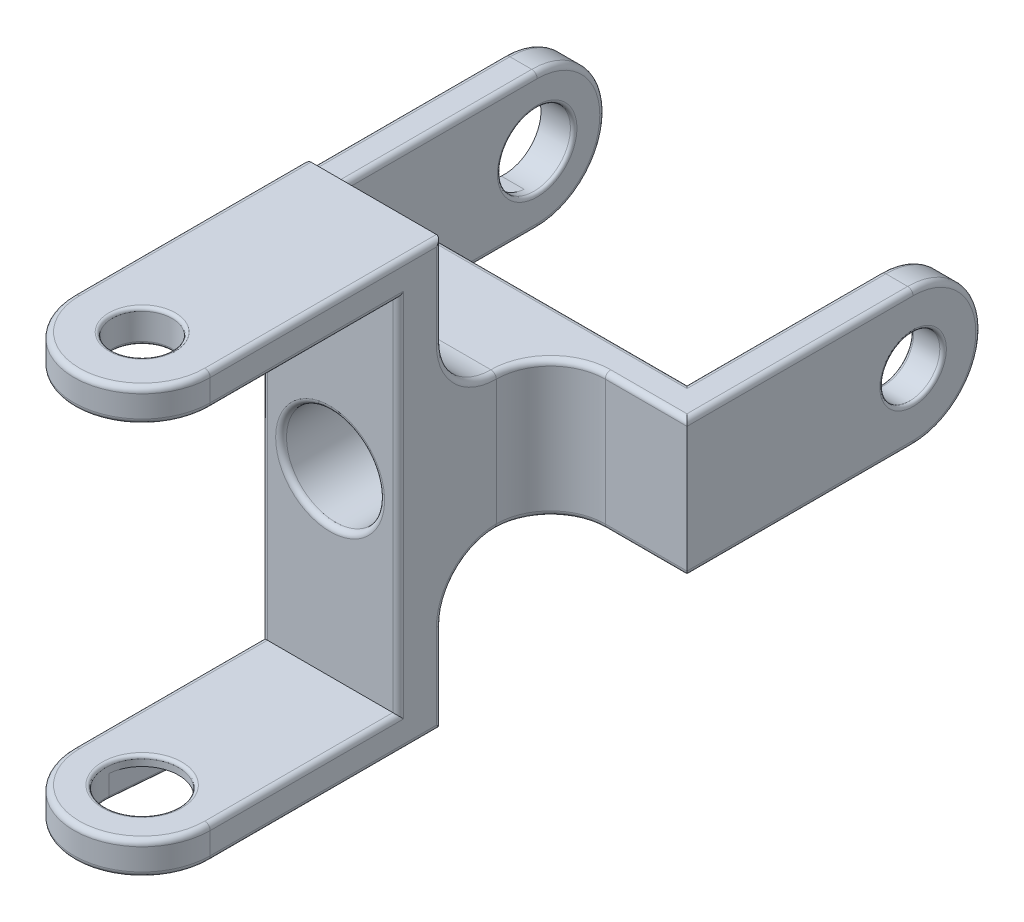
SolidWorks part; units mm, degrees
material "聚脂树脂"
ref_plane "前视基准面" through (0, 0, 0) normal (0, 0, 1) x (1, 0, 0)
ref_plane "上视基准面" through (0, 0, 0) normal (0, 1, 0) x (1, 0, 0)
ref_plane "右视基准面" through (0, 0, 0) normal (1, 0, 0) x (0, 0, -1)
sketch "草图1" plane through (0, 0, 0) normal (0, 0, 1) x (1, 0, 0)
  line L1 (-6.25, -19.5) -> (6.25, -19.5)
  line L2 (-6.25, -19.5) -> (-6.25, 19.5)
  line L3 (-6.25, 19.5) -> (6.25, 19.5)
  line L4 (6.25, -19.5) -> (6.25, 19.5)
  line L5 (-6.25, -19.5) -> (6.25, 19.5) construction
  line L6 (-6.25, 19.5) -> (6.25, -19.5) construction
  point P0 (0, 0)
  dimension "D1" = 12.5
  dimension "D2" = 39
extrude "凸台-拉伸1" add sketch "草图1" along normal blind 4
sketch "草图2" plane through (0, 0, 4) normal (0, 0, 1) x (1, 0, 0)
  line L0 (6.25, -19.5) -> (6.25, 19.5) construction
  line L1 (-6.25, 19.5) -> (6.25, 19.5)
  line L2 (-6.25, 19.5) -> (-6.25, 16.5)
  line L3 (-6.25, 16.5) -> (6.25, 16.5)
  line L4 (6.25, 19.5) -> (6.25, 16.5)
  line L5 (-6.25, 19.5) -> (-6.25, -19.5) construction
  line L6 (-6.25, -16.5) -> (6.25, -16.5)
  line L7 (-6.25, -16.5) -> (-6.25, -19.5)
  line L8 (-6.25, -19.5) -> (6.25, -19.5)
  line L9 (6.25, -16.5) -> (6.25, -19.5)
  dimension "D1" = 3
  dimension "D2" = 3
extrude "凸台-拉伸2" add sketch "草图2" along normal blind 17.25
sketch "草图5" plane through (0, 19.5, 0) normal (0, 1, 0) x (1, 0, 0)
  line L0 (6.25, -21.25) -> (-6.25, -21.25) construction
  circle A0 centre (0, -21.25) radius 6.25
extrude "凸台-拉伸3" add sketch "草图5" against normal blind 3
sketch "草图6" plane through (0, -19.5, 0) normal (0, -1, 0) x (1, 0, 0)
  line L0 (-6.25, 21.25) -> (6.25, 21.25) construction
  circle A0 centre (0, 21.25) radius 6.25
extrude "凸台-拉伸4" add sketch "草图6" against normal blind 3
sketch "草图7" plane through (0, 0, 0) normal (0, 0, -1) x (-1, 0, 0)
  line L0 (6.25, 19.5) -> (6.25, -19.5) construction
  line L1 (-6.25, -6.25) -> (6.25, -6.25)
  line L2 (-6.25, -6.25) -> (-6.25, 6.25)
  line L3 (-6.25, 6.25) -> (6.25, 6.25)
  line L4 (6.25, -6.25) -> (6.25, 6.25)
  line L5 (-6.25, -6.25) -> (6.25, 6.25) construction
  line L6 (-6.25, 6.25) -> (6.25, -6.25) construction
  point P0 (0, 0)
  dimension "D1" = 12.5
extrude "凸台-拉伸5" add sketch "草图7" along normal blind 10
sketch "草图8" plane through (0, 0, -10) normal (0, 0, -1) x (-1, 0, 0)
  line L1 (-18.75, -6.25) -> (18.75, -6.25)
  line L2 (-18.75, -6.25) -> (-18.75, 6.25)
  line L3 (-18.75, 6.25) -> (18.75, 6.25)
  line L4 (18.75, -6.25) -> (18.75, 6.25)
  line L5 (-18.75, -6.25) -> (18.75, 6.25) construction
  line L6 (-18.75, 6.25) -> (18.75, -6.25) construction
  point P0 (0, 0)
  dimension "D1" = 12.5
  dimension "D2" = 37.5
extrude "凸台-拉伸6" add sketch "草图8" along normal blind 3
sketch "草图9" plane through (0, 0, -13) normal (0, 0, -1) x (-1, 0, 0)
  line L0 (-18.75, 6.25) -> (-18.75, -6.25) construction
  line L1 (-18.75, 6.25) -> (-15.75, 6.25)
  line L2 (-18.75, 6.25) -> (-18.75, -6.25)
  line L3 (-18.75, -6.25) -> (-15.75, -6.25)
  line L4 (-15.75, 6.25) -> (-15.75, -6.25)
  line L5 (-18.75, -6.25) -> (18.75, -6.25) construction
  line L6 (18.75, 6.25) -> (-18.75, 6.25) construction
  line L7 (18.75, -6.25) -> (15.75, -6.25)
  line L8 (18.75, -6.25) -> (18.75, 6.25)
  line L9 (18.75, 6.25) -> (15.75, 6.25)
  line L10 (15.75, -6.25) -> (15.75, 6.25)
  dimension "D1" = 3
  dimension "D2" = 3
extrude "凸台-拉伸7" add sketch "草图9" along normal blind 17.75
sketch "草图10" plane through (18.75, 0, 0) normal (1, 0, 0) x (0, 0, -1)
  line L0 (30.75, 6.25) -> (30.75, -6.25) construction
  circle A0 centre (30.75, 0) radius 6.25
extrude "凸台-拉伸8" add sketch "草图10" against normal blind 3
sketch "草图11" plane through (-18.75, 0, 0) normal (-1, 0, 0) x (0, 0, 1)
  line L0 (-30.75, -6.25) -> (-30.75, 6.25) construction
  circle A0 centre (-30.75, 0) radius 6.25
extrude "凸台-拉伸9" add sketch "草图11" against normal blind 3
fillet "圆角1" radius 5 4 edges at (0, -6.25, 0) (6.25, 0, -10) (0, 6.25, 0) (-6.25, 0, -10)
sketch "草图15" plane through (-18.75, 0, 0) normal (-1, 0, 0) x (0, 0, 1)
  line L0 (-30.4569, 3.3372) -> (-14.5794, 1.9425)
  line L1 (-30.4569, -3.3372) -> (-14.5794, -1.9425)
  arc A0 (-30.4569, 3.3372) -> (-30.4569, -3.3372) centre (-30.75, 0) ccw
  arc A1 (-14.5794, -1.9425) -> (-14.5794, 1.9425) centre (-14.75, 0) ccw
  dimension "D1" = 6.7
  dimension "D2" = 3.9
  dimension "D3" = 16
extrude "切除-拉伸4" cut sketch "草图15" against normal blind 2.1
sketch "草图16" plane through (-16.65, 0, 0) normal (-1, 0, 0) x (0, 0, 1)
  circle A0 centre (-30.75, 0) radius 3.35
extrude "切除-拉伸5" cut sketch "草图16" against normal up to next
sketch "草图17" plane through (18.75, 0, 0) normal (1, 0, 0) x (0, 0, -1)
  circle A0 centre (30.75, 0) radius 2.75
  dimension "D1" = 5.5
extrude "切除-拉伸6" cut sketch "草图17" against normal up to next
fillet "圆角2" radius 0.5 36 edges at (15, 6.25, -10) (7.7145, 6.25, -8.5355) (15, -6.25, -10) (7.7145, -6.25, -8.5355) (0, 19.5, 27.5) (0, 16.5, 27.5) (0, -16.5, 27.5) (0, -19.5, 27.5) (-15, -6.25, -10) (-7.7145, -6.25, -8.5355) (-15, 6.25, -10) (-7.7145, 6.25, -8.5355) (-18.75, 6.25, -20.375) (-18.75, -6.25, -20.375) (18.75, 6.25, -20.375) (18.75, 0, -37) (6.25, -19.5, 10.625) (6.25, -16.5, 12.625) (6.25, 0, 4) (6.25, 16.5, 12.625) (6.25, 19.5, 10.625) (6.25, 15.375, 0) (6.25, 7.7145, -1.4645) (6.25, -7.7145, -1.4645) (6.25, -15.375, 0) (-6.25, 19.5, 10.625) (-6.25, 16.5, 12.625) (-6.25, 0, 4) (-6.25, -16.5, 12.625) (-6.25, -19.5, 10.625) (-6.25, -15.375, 0) (-6.25, -7.7145, -1.4645) (-6.25, 7.7145, -1.4645) (-6.25, 15.375, 0) (-18.75, 0, -37) (18.75, -6.25, -20.375)
fillet "圆角3" radius 0.5 8 edges at (-15.75, 6.25, -21.875) (-15.75, 0, -37) (15.75, 6.25, -21.875) (15.75, 0, -37) (-15.75, -6.25, -21.875) (15.75, -6.25, -21.875) (0, -6.25, -13) (0, 6.25, -13)
sketch "草图18" plane through (0, -19.5, 0) normal (0, -1, 0) x (1, 0, 0)
  line L0 (-3.3372, 20.9569) -> (-1.9425, 5.0794)
  line L1 (3.3372, 20.9569) -> (1.9425, 5.0794)
  arc A0 (3.3372, 20.9569) -> (-3.3372, 20.9569) centre (0, 21.25) ccw
  arc A1 (-1.9425, 5.0794) -> (1.9425, 5.0794) centre (0, 5.25) ccw
  dimension "D1" = 6.7
  dimension "D2" = 3.9
  dimension "D3" = 16
extrude "切除-拉伸7" cut sketch "草图18" against normal blind 2.1
sketch "草图19" plane through (0, -17.4, 0) normal (0, -1, 0) x (1, 0, 0)
  circle A0 centre (0, 21.25) radius 3.35
extrude "切除-拉伸8" cut sketch "草图19" against normal up to next
sketch "草图20" plane through (0, 19.5, 0) normal (0, 1, 0) x (1, 0, 0)
  circle A0 centre (0, -21.25) radius 2.75
  dimension "D1" = 5.5
extrude "切除-拉伸9" cut sketch "草图20" against normal up to next
fillet "圆角4" radius 0.3 7 edges at (0, -19.5, 24.6) (2.6398, -19.5, 13.0181) (0, -19.5, 3.3) (0, 16.5, 24) (0, 19.5, 24) (3.35, -16.5, 21.25) (-2.6398, -19.5, 13.0181)
sketch "草图21" plane through (0, 0, 4) normal (0, 0, 1) x (1, 0, 0)
  circle A0 centre (0, 0) radius 4.5
  dimension "D1" = 9
extrude "切除-拉伸10" cut sketch "草图21" against normal through all
fillet "圆角5" radius 0.5 2 edges at (4.5, 0, 4) (4.5, 0, -13)
fillet "圆角6" radius 0.3 3 edges at (15.75, 0, -33.5) (18.75, 0, -33.5) (-15.75, 0, -27.4)
